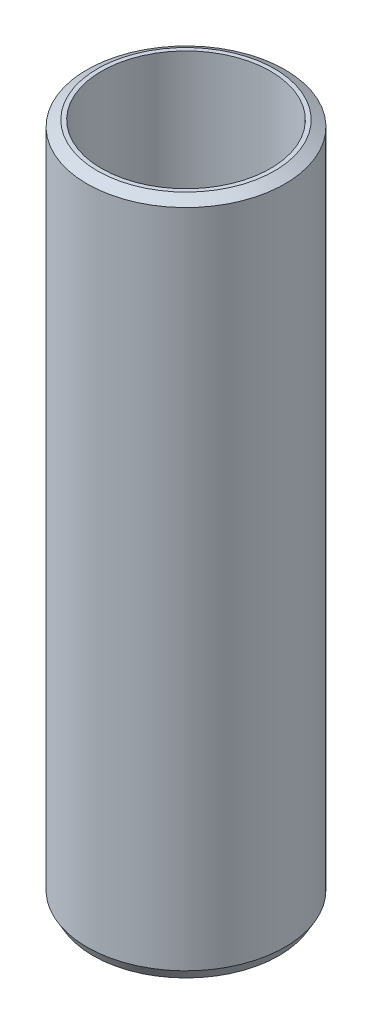
SolidWorks part; units mm, degrees
ref_plane "Front Plane" through (0, 0, 0) normal (0, 0, 1) x (1, 0, 0)
ref_plane "Top Plane" through (0, 0, 0) normal (0, 1, 0) x (1, 0, 0)
ref_plane "Right Plane" through (0, 0, 0) normal (1, 0, 0) x (0, 0, -1)
sketch "Sketch1" plane through (0, 0, 0) normal (0, 1, 0) x (1, 0, 0)
  circle A0 centre (0, 0) radius 55
  dimension "SHAFT_OD" = 110
extrude "Boss-Extrude1" add sketch "Sketch1" along normal blind 376.4752
sketch "Sketch2" plane through (0, 0, 0) normal (0, 1, 0) x (1, 0, 0)
  circle A0 centre (0, 0) radius 46.9107
  dimension "BORE_D" = 93.8214
extrude "Cut-Extrude1" cut sketch "Sketch2" along normal through all
chamfer "Chamfer1" distance 3.3465 angle 60 2 edges at (0, 376.4752, 55) (0, 0, 55) first distance on face at (0, 376.4752, 55) first distance on face at (0, 0, 46.9107)
